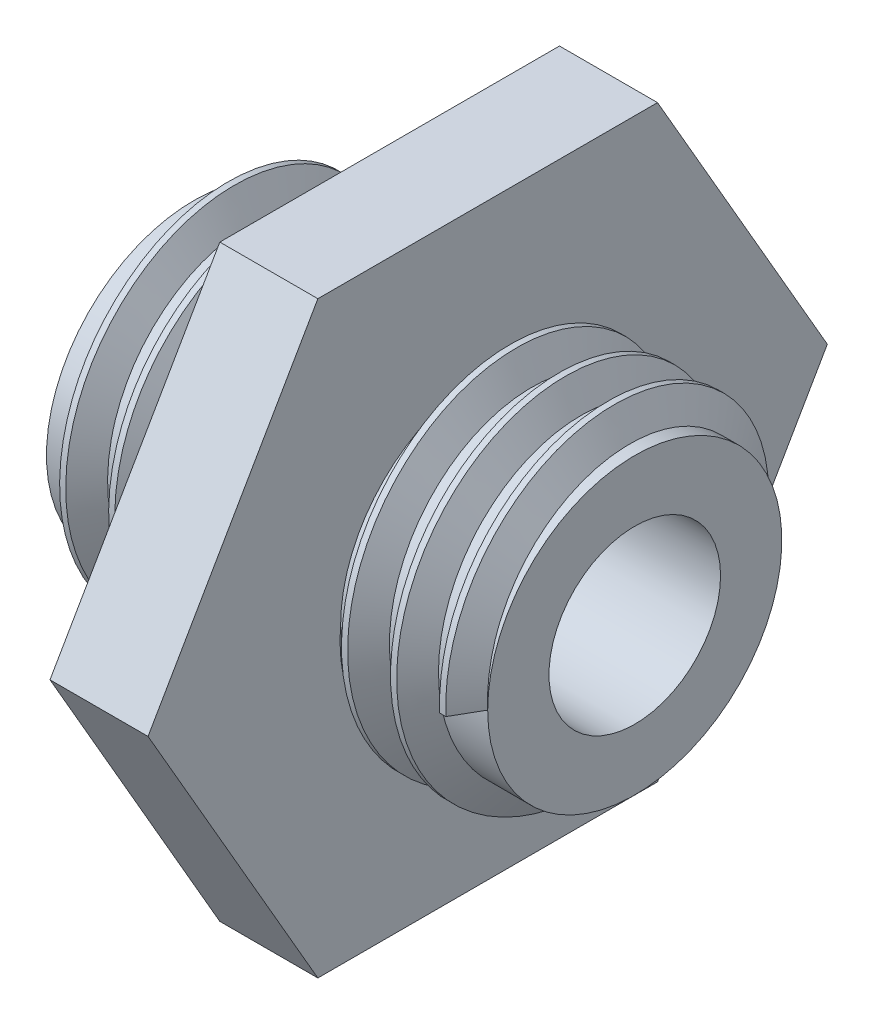
SolidWorks part; units mm, degrees
ref_plane "Front Plane" through (0, 0, 0) normal (0, 0, 1) x (1, 0, 0)
ref_plane "Top Plane" through (0, 0, 0) normal (0, 1, 0) x (1, 0, 0)
ref_plane "Right Plane" through (0, 0, 0) normal (1, 0, 0) x (0, 0, -1)
sketch "Sketch1" plane through (0, 0, 0) normal (1, 0, 0) x (0, 0, -1)
  line L1 (6.9282, 0) -> (3.4641, 6)
  line L2 (3.4641, 6) -> (-3.4641, 6)
  line L3 (-3.4641, 6) -> (-6.9282, 0)
  line L4 (-6.9282, 0) -> (-3.4641, -6)
  line L5 (-3.4641, -6) -> (3.4641, -6)
  line L6 (3.4641, -6) -> (6.9282, 0)
  circle A0 centre (0, 0) radius 6 construction
  circle A1 centre (0, 0) radius 3
  dimension "D1" = 12
  dimension "D2" = 6
extrude "Boss-Extrude1" add sketch "Sketch1" along normal mid plane 2
sketch "Sketch2" plane through (0, 0, 0) normal (1, 0, 0) x (0, 0, -1)
  circle A0 centre (0, 0) radius 3
  circle A1 centre (0, 0) radius 1.75
  dimension "D1" = 3.5
  dimension "D2" = 6
extrude "Boss-Extrude2" add sketch "Sketch2" along normal blind 4 and the other way blind 5
thread "Thread1" pitch 1 method extrude profile "Thread Profile1" start angle 0, offset 0, length 0, pitch 1, diameter 6
ref_plane "Plane1" through (4, 0, 3) normal (0, -1, 0) x (0, 0, 1)
sketch "Thread Profile1" plane through (4, 0, 3) normal (0, -1, 0) x (0, 0, 1)
  line L0 (0, 0) -> (0, 1) construction
  line L1 (0, 0) -> (0.5413, 0.3125)
  line L2 (0.5413, 0.3125) -> (0.5413, 0.4375)
  line L3 (0.5413, 0.4375) -> (0, 0.75)
  line L4 (0.5413, 0.375) -> (0, 0.375) construction
  line L11 (0, 0) -> (0, 0.75)
  point P2 (0, 0)
  dimension "Pitch" = 1
  dimension "Profile_Angle" = 60
  dimension "Profile_Land" = 0.125
  dimension "Profile_Height" = 0.5413
thread "Thread2" pitch 1 method extrude profile "Thread Profile2" start angle 0, offset 0, length 0, pitch 1, diameter 6
ref_plane "Plane2" through (-5, 0, -3) normal (0, -1, 0) x (0, 0, -1)
sketch "Thread Profile2" plane through (-5, 0, -3) normal (0, -1, 0) x (0, 0, -1)
  line L0 (0, 0) -> (0, 1) construction
  line L1 (0, 0) -> (0.5413, 0.3125)
  line L2 (0.5413, 0.3125) -> (0.5413, 0.4375)
  line L3 (0.5413, 0.4375) -> (0, 0.75)
  line L4 (0.5413, 0.375) -> (0, 0.375) construction
  line L11 (0, 0) -> (0, 0.75)
  point P2 (0, 0)
  dimension "Pitch" = 1
  dimension "Profile_Angle" = 60
  dimension "Profile_Land" = 0.125
  dimension "Profile_Height" = 0.5413
